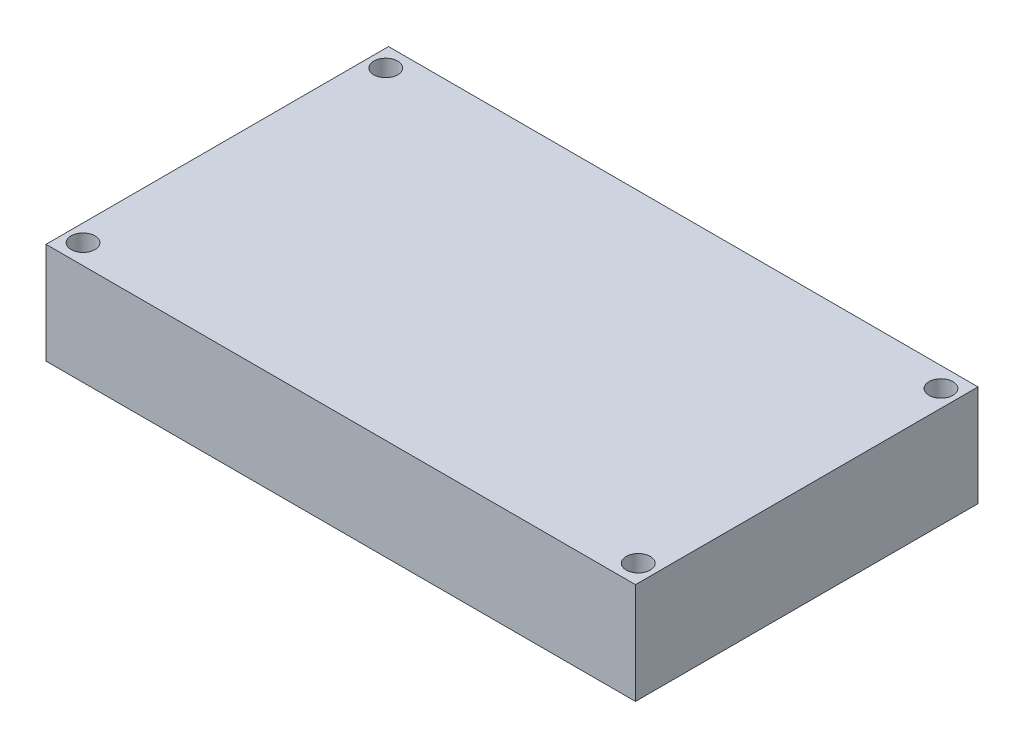
SolidWorks part; units mm, degrees
ref_plane "Front Plane" through (0, 0, 0) normal (0, 0, 1) x (1, 0, 0)
ref_plane "Top Plane" through (0, 0, 0) normal (0, 1, 0) x (1, 0, 0)
ref_plane "Right Plane" through (0, 0, 0) normal (1, 0, 0) x (0, 0, -1)
sketch "Sketch1" plane through (0, 0, 0) normal (0, 1, 0) x (1, 0, 0)
  line L0 (0, 43) -> (74, 0) construction
  line L1 (0, 0) -> (74, 0)
  line L2 (0, 0) -> (0, 43)
  line L3 (0, 43) -> (74, 43)
  line L4 (74, 0) -> (74, 43)
  line L6 (2.15, 40.5) -> (71.85, 40.5) construction
  line L7 (2.15, 40.5) -> (2.15, 2.5) construction
  line L8 (2.15, 2.5) -> (71.85, 2.5) construction
  line L9 (71.85, 40.5) -> (71.85, 2.5) construction
  line L10 (2.15, 40.5) -> (71.85, 2.5) construction
  line L11 (2.15, 2.5) -> (71.85, 40.5) construction
  circle A0 centre (2.15, 40.5) radius 1.5
  circle A1 centre (71.85, 40.5) radius 1.5
  circle A2 centre (71.85, 2.5) radius 1.5
  circle A3 centre (2.15, 2.5) radius 1.5
  point P5 (37, 21.5)
  dimension "D3" = 3
  dimension "D1" = 74
  dimension "D2" = 43
  dimension "D4" = 38
  dimension "D5" = 69.7
extrude "Boss-Extrude1" add sketch "Sketch1" along normal blind 12.7
ref_plane "Plane1" through (37, 0, 0) normal (-1, 0, 0) x (0, 0, 1)
ref_plane "Plane2" through (0, 0, -21.5) normal (0, 0, -1) x (-1, 0, 0)
